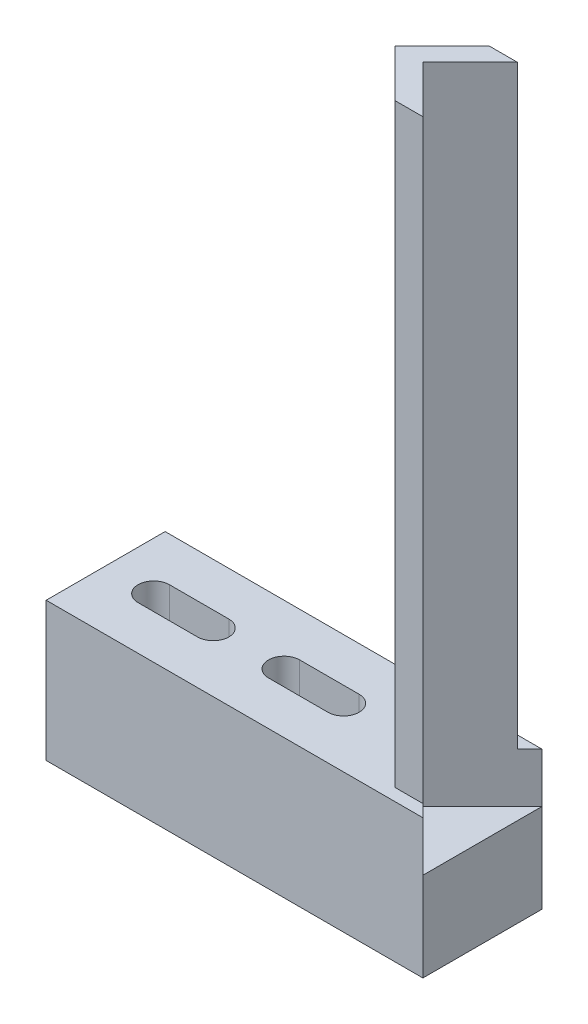
SolidWorks part; units mm, degrees
ref_plane "Front Plane" through (0, 0, 0) normal (0, 0, 1) x (1, 0, 0)
ref_plane "Top Plane" through (0, 0, 0) normal (0, 1, 0) x (1, 0, 0)
ref_plane "Right Plane" through (0, 0, 0) normal (1, 0, 0) x (0, 0, -1)
sketch "Sketch1" plane through (0, 0, 0) normal (0, 0, 1) x (1, 0, 0)
  line L0 (0, 0) -> (48.26, 0)
  line L6 (0, 0) -> (0, 17.78)
  line L10 (0, 17.78) -> (48.26, 17.78)
  line L11 (48.26, 0) -> (48.26, 17.78)
  dimension "D1" = 48.26
  dimension "D2" = 17.78
extrude "Boss-Extrude1" add sketch "Sketch1" against normal blind 15.24
sketch "Sketch3" plane through (0, 17.78, 0) normal (0, 1, 0) x (1, 0, 0)
  line L0 (48.26, 15.24) -> (40.64, 7.62)
  line L1 (40.64, 7.62) -> (48.26, 0)
  line L2 (43.0937, 13.6658) -> (37.0479, 7.62)
  line L4 (48.26, 15.24) -> (48.26, 0)
  line L5 (37.0479, 7.62) -> (43.0937, 1.5742)
  line L9 (43.0937, 13.6658) -> (46.6858, 13.6658)
  line L11 (43.0937, 1.5742) -> (46.6858, 1.5742)
  line L12 (48.26, 0) -> (0, 0) construction
  line L13 (48.26, 15.24) -> (0, 15.24) construction
  line M1 (0, 0) -> (48.26, 0)
  line M2 (48.26, 0) -> (48.26, 15.24)
  line M3 (48.26, 15.24) -> (0, 15.24)
  dimension "D1" = 90
  dimension "D2" = 90
  dimension "D3" = 8.55
  dimension "D4" = 8.55
  dimension "D6" = 2.54
extrude "Cut-Extrude1" cut sketch "Sketch3" against normal blind 6.38 contours L0 L1 M2 region at (45.72, 17.78, -7.62)
sketch "Sketch4" plane through (0, 17.78, 0) normal (0, 1, 0) x (1, 0, 0)
  line L0 (30.48, 7.62) -> (22.86, 7.62) construction
  line L1 (30.48, 5.62) -> (22.86, 5.62)
  line L2 (30.48, 9.62) -> (22.86, 9.62)
  line L3 (13.78, 7.62) -> (6.16, 7.62) construction
  line L4 (13.78, 5.62) -> (6.16, 5.62)
  line L5 (13.78, 9.62) -> (6.16, 9.62)
  line L6 (48.26, 0) -> (0, 0) construction
  arc A0 (30.48, 5.62) -> (30.48, 9.62) centre (30.48, 7.62) ccw
  arc A1 (22.86, 9.62) -> (22.86, 5.62) centre (22.86, 7.62) ccw
  arc A2 (13.78, 5.62) -> (13.78, 9.62) centre (13.78, 7.62) ccw
  arc A3 (6.16, 9.62) -> (6.16, 5.62) centre (6.16, 7.62) ccw
  point P2 (26.67, 7.62)
  point P7 (9.97, 7.62)
  point P14 (32.48, 7.62)
  point P16 (4.16, 7.62)
  point P18 (15.78, 7.62)
  point P19 (20.86, 7.62)
  point P20 (0, 0)
  point P21 (0, 0)
  dimension "D1" = 4
  dimension "D2" = 10.16
  dimension "D3" = 7.62
  dimension "D4" = 7.62
  dimension "D5" = 5.08
extrude "Cut-Extrude2" cut sketch "Sketch4" against normal through all
extrude "Boss-Extrude2" add sketch "Sketch3<3>" along normal blind 76.2 contours L2 L5 L1 L0 M1 M3 region at (43.5535, 17.78, -10.7522)
sketch "Sketch3<3>" plane through (0, 17.78, 0) normal (0, 1, 0) x (1, 0, 0) same geometry as "Sketch3"
